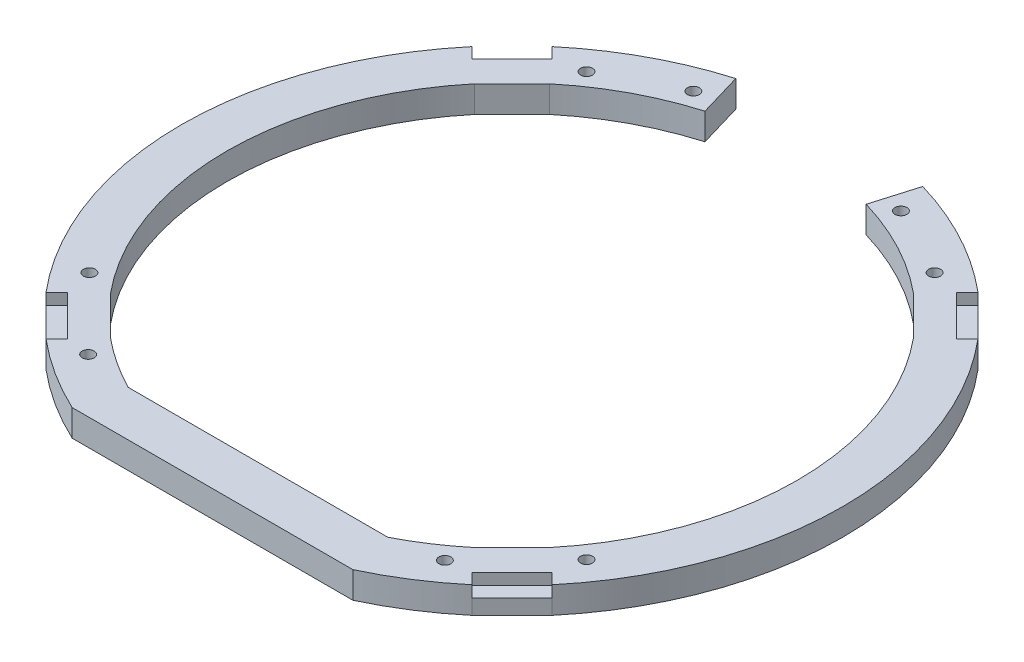
SolidWorks part; units mm, degrees
ref_plane "Plano frontal" through (0, 0, 0) normal (0, 0, 1) x (1, 0, 0)
ref_plane "Plano superior" through (0, 0, 0) normal (0, 1, 0) x (1, 0, 0)
ref_plane "Plano direito" through (0, 0, 0) normal (1, 0, 0) x (0, 0, -1)
sketch "Esboço1" plane through (0, 0, 0) normal (0, 1, 0) x (1, 0, 0)
  line L0 (-37, -78.961) -> (37, -78.961)
  line L1 (0, 0) -> (0, 46.3203) construction
  line L2 (-61.4312, 61.4312) -> (0, 0) construction
  line L3 (0, 0) -> (-61.4312, -61.4312) construction
  line L4 (-66.7345, -56.1279) -> (-56.1279, -66.7345)
  line L5 (-66.7345, 56.1279) -> (-56.1279, 66.7345)
  line L6 (66.7345, -56.1279) -> (56.1279, -66.7345)
  line L7 (66.7345, 56.1279) -> (56.1279, 66.7345)
  arc A0 (37, -78.961) -> (56.1279, -66.7345) centre (0, 0) ccw
  arc A1 (-66.7345, 56.1279) -> (-66.7345, -56.1279) centre (0, 0) ccw
  arc A2 (-56.1279, -66.7345) -> (-37, -78.961) centre (0, 0) ccw
  arc A3 (56.1279, 66.7345) -> (-56.1279, 66.7345) centre (0, 0) ccw
  arc A4 (66.7345, -56.1279) -> (66.7345, 56.1279) centre (0, 0) ccw
  point P13 (-61.4312, -61.4312)
  point P14 (-61.4312, 61.4312)
  dimension "D1" = 174.4
  dimension "D2" = 74
  dimension "D3" = 45
  dimension "D4" = 45
  dimension "D5" = 7.5
  dimension "D6" = 7.5
extrude "Ressalto-extrusão1" add sketch "Esboço1" along normal blind 7
shell "Casca1" thickness 12 removed face at (0, 0, 13.8707) removed face at (0, 7, 13.8707)
hole_wizard "Furo roscado para conduíte de M3x0.51" positions "Esboço2" profile "Esboço4" tap size "M3x0.5" standard "Helicoil® Metric" end condition through all
sketch "Esboço2" plane through (0, 7, 0) normal (0, 1, 0) x (1, 0, 0)
  line L0 (0, 0) -> (0, -27.908) construction
  line L2 (-27.3616, 75.1754) -> (0, 0) construction
  line L3 (0, 0) -> (-47.0228, -64.7214) construction
  line L4 (-45.8861, 65.5322) -> (0, 0) construction
  line L5 (0, 0) -> (-65.5322, -45.8861) construction
  point P0 (-27.3616, 75.1754)
  point P6 (-47.0228, -64.7214)
  point P26 (47.0228, -64.7214)
  point P27 (27.3616, 75.1754)
  point P28 (-65.5322, -45.8861)
  point P30 (-45.8861, 65.5322)
  point P40 (65.5322, -45.8861)
  point P41 (45.8861, 65.5322)
  dimension "D1" = 20
  dimension "D2" = 36
  dimension "D3" = 80
  dimension "D4" = 80
  dimension "D5" = 35
  dimension "D6" = 55
  dimension "D7" = 80
  dimension "D8" = 80
sketch "Esboço4" plane through (-27.3616, 7, -75.1754) normal (1, 0, 0) x (0, 0, 1)
  line L0 (0, 0) -> (0, 7)
  line L1 (0, 7) -> (1.575, 7)
  line L2 (1.575, 7) -> (1.575, 0)
  line L5 (1.575, 0) -> (0, 0)
  line L11 (0, -6.35) -> (0, 107.95) construction
  dimension "Thru Tap Drill Dia." = 3.15
  dimension "Thru Tap Drill Depth" = 7
cosmetic thread "Rosca de furo1" parameters "D1"=10, "D2"=3.716
cosmetic thread "Rosca de furo2" parameters "D1"=10, "D2"=3.716
cosmetic thread "Rosca de furo3" parameters "D1"=10, "D2"=3.716
cosmetic thread "Rosca de furo4" parameters "D1"=10, "D2"=3.716
cosmetic thread "Rosca de furo5" parameters "D1"=10, "D2"=3.716
cosmetic thread "Rosca de furo6" parameters "D1"=10, "D2"=3.716
cosmetic thread "Rosca de furo7" parameters "D1"=10, "D2"=3.716
cosmetic thread "Rosca de furo8" parameters "D1"=10, "D2"=3.716
sketch "Esboço5" plane through (0, 7, 0) normal (0, 1, 0) x (1, 0, 0)
  line L0 (-24.6445, 83.645) -> (-21.2531, 72.1342)
  line L1 (24.6445, 83.645) -> (21.2531, 72.1342)
  line L2 (0, 0) -> (-24.6445, 83.645) construction
  line L3 (0, 0) -> (24.6445, 83.645) construction
  arc A0 (37, -78.961) -> (56.1279, -66.7345) centre (0, 0) ccw construction
  arc A1 (34.2237, -66.961) -> (48.0218, -57.8701) centre (0, 0) ccw construction
  circle A2 centre (-27.3616, 75.1754) radius 1.575 construction
  circle A3 centre (27.3616, 75.1754) radius 1.575 construction
  arc A4 (-21.2531, 72.1342) -> (21.2531, 72.1342) centre (0, 0) cw
  arc A5 (-24.6445, 83.645) -> (24.6445, 83.645) centre (0, 0) cw
  dimension "D1" = 5
  dimension "D2" = 5
extrude "Corte-extrusão1" cut sketch "Esboço5" against normal through all
sketch "Esboço8" plane through (0, 7, 0) normal (0, 1, 0) x (1, 0, 0)
  line L0 (0, 0) -> (0, 63.2396) construction
  line L1 (-145.1736, 145.1736) -> (0, 0) construction
  line L2 (0, 0) -> (-144.4428, -144.4428) construction
  line L3 (-66.7345, -56.1279) -> (-63.9061, -53.2995)
  line L4 (-63.9061, -53.2995) -> (-53.2995, -63.9061)
  line L5 (-56.1279, -66.7345) -> (-53.2995, -63.9061)
  line L6 (-66.7345, -56.1279) -> (-56.1279, -66.7345)
  line L7 (-56.1279, 66.7345) -> (-53.2995, 63.9061)
  line L8 (-53.2995, 63.9061) -> (-63.9061, 53.2995)
  line L9 (-66.7345, 56.1279) -> (-63.9061, 53.2995)
  line L10 (-66.7345, 56.1279) -> (-56.1279, 66.7345)
  line L11 (66.7345, -56.1279) -> (63.9061, -53.2995)
  line L12 (63.9061, -53.2995) -> (53.2995, -63.9061)
  line L13 (56.1279, -66.7345) -> (53.2995, -63.9061)
  line L14 (66.7345, -56.1279) -> (56.1279, -66.7345)
  line L15 (66.7345, 56.1279) -> (63.9061, 53.2995)
  line L16 (53.2995, 63.9061) -> (63.9061, 53.2995)
  line L17 (56.1279, 66.7345) -> (53.2995, 63.9061)
  line L18 (66.7345, 56.1279) -> (56.1279, 66.7345)
  point P14 (-58.6028, -58.6028)
  point P19 (-58.6028, 58.6028)
  dimension "D1" = 45
  dimension "D2" = 45
  dimension "D3" = 4
  dimension "D4" = 4
extrude "Corte-extrusão2" cut sketch "Esboço8" against normal blind 3
